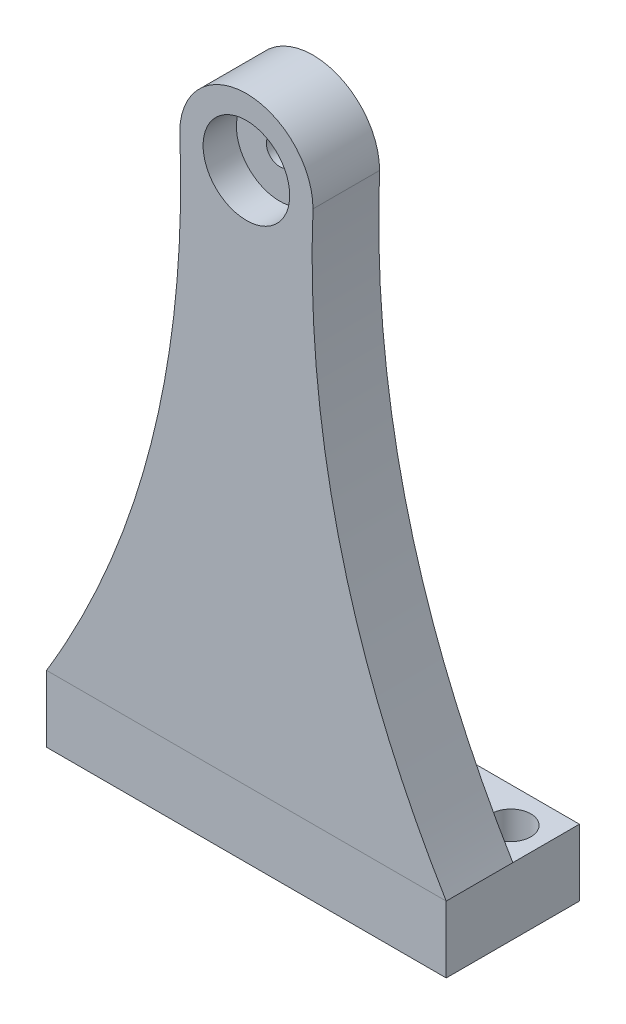
SolidWorks part; units mm, degrees
note: The reader was unsure of these and kept them because the rebuilt part matched: thickness of "Taban-Flanş1", "Taban-Flanş2", "Sac-Levha1", "Sac-Levha2", "Sheet-Metal27", "Sheet-Metal28", "Sheet-Metal29".
other "Markup1"
sketch "Sketch1" plane through (40, 90, 0) normal (0.9714, 0.2368, 0.0146) x (0.0441, -0.1197, -0.9918)
ref_plane "Ön Düzlem" through (0, 0, 0) normal (0, 0, 1) x (1, 0, 0)
ref_plane "Üst Düzlem" through (0, 0, 0) normal (0, 1, 0) x (1, 0, 0)
ref_plane "Sağ Düzlem" through (0, 0, 0) normal (1, 0, 0) x (0, 0, -1)
sketch "Çizim1" plane through (0, 0, 0) normal (0, 0, 1) x (1, 0, 0)
  line L0 (-100, 0) -> (200, 0)
  arc A0 (0, 400) -> (100, 400) centre (50, 400) cw
  circle A1 centre (50, 400) radius 10
  spline S0 degree 2 poles (-100, 0) (8.8172, 180.8736) (0, 400) knots 0 0 0 1 1 1
  spline S1 degree 2 poles (200, 0) (91.1828, 180.8736) (100, 400) knots 0 0 0 1 1 1
  point P42 (50, 400)
  dimension "D9" = 20
  dimension "D1" = 100
  dimension "D2" = 100
  dimension "D3" = 50
  dimension "D4" = 200
  dimension "D5" = 200
  dimension "D6" = 100
  dimension "D7" = 100
  dimension "D8" = 400
base flange "Taban-Flanş1" sketch "Çizim1" thickness 50 reverse thickness direction no parameters "D1"=0.7366
sketch "Çizim6" plane through (0, 0, 0) normal (0, 1, 0) x (1, 0, 0)
  line L0 (-100, 0) -> (-100, 100)
  line L1 (-100, 100) -> (200, 100)
  line L2 (200, 100) -> (200, 0)
  line L3 (-100, 0) -> (200, 0)
  circle A0 centre (-75, 73.5) radius 15
  circle A1 centre (175, 73.5) radius 15
  dimension "D3" = 30
  dimension "D4" = 30
  dimension "D1" = 300
  dimension "D2" = 100
  dimension "D5" = 25
  dimension "D6" = 25
  dimension "D7" = 73.5
  dimension "D8" = 73.5
base flange "Taban-Flanş2" sketch "Çizim6" thickness 50 reverse thickness direction no parameters "D1"=0.7366
scale "Scale1" bodies to scale 102 101 scale about origin uniform scaling yes scale factor 0.2
sketch "Sketch3" plane through (0, 0, 0) normal (0, 0, 1) x (1, 0, 0)
  circle A0 centre (10, 80) radius 6.5
  dimension "D1" = 13
extrude "Cut-Extrude1" cut sketch "Sketch3" against normal blind 5
sketch "Büküm-Çizgileri1" [suppressed] plane through (0, 0, 0) normal (0, 1, 0) x (1, 0, 0)
sketch "Sınırlandırma-Kutusu1" [suppressed] plane through (0, 0, 0) normal (0, 1, 0) x (1, 0, 0)
sheet metal parameters "Sac-Levha1" thickness 50 parameters "D1"=0.7366
flat pattern "Düz-Çoğaltma1" [suppressed]
sketch "Büküm-Çizgileri2" plane through (0, 0, 0) normal (0, 1, 0) x (1, 0, 0)
sketch3d "Sınırlandırma-Kutusu2" [suppressed]
  line L0 (220.5914, 259.5632, 0) -> (220.5914, -190.4368, 0) construction
  line L1 (-79.4086, 259.5632, 0) -> (-79.4086, -190.4368, 0) construction
  line L2 (220.5914, 259.5632, 0) -> (-79.4086, 259.5632, 0) construction
  line L3 (220.5914, -190.4368, 0) -> (-79.4086, -190.4368, 0) construction
sheet metal parameters "Sac-Levha2" thickness 50 parameters "D1"=0.7366
flat pattern "Düz-Çoğaltma2"
sketch "Büküm-Çizgileri3"
sketch3d "Sınırlandırma-Kutusu3" [suppressed]
  line L0 (-100, 50, 0) -> (200, 50, 0) construction
  line L1 (-100, 0, 0) -> (200, 0, 0) construction
  line L2 (-100, 50, 0) -> (-100, 0, 0) construction
  line L3 (200, 50, 0) -> (200, 0, 0) construction
sheet metal parameters "Sheet-Metal27" thickness 50 parameters "D1"=0.7366
flat pattern "Düz-Çoğaltma2"
sketch "Büküm-Çizgileri3"
sketch3d "Sınırlandırma-Kutusu3" [suppressed]
  line L0 (-100, 50, 0) -> (200, 50, 0) construction
  line L1 (-100, 0, 0) -> (200, 0, 0) construction
  line L2 (-100, 50, 0) -> (-100, 0, 0) construction
  line L3 (200, 50, 0) -> (200, 0, 0) construction
sheet metal parameters "Sheet-Metal28" thickness 50 parameters "D1"=0.7366, "D7"=0.7366
flat pattern "Düz-Çoğaltma1"
sketch "Büküm-Çizgileri2" plane through (0, 0, 0) normal (0, 1, 0) x (1, 0, 0)
sketch3d "Sınırlandırma-Kutusu2" [suppressed]
  line L0 (220.5914, 259.5632, 0) -> (220.5914, -190.4368, 0) construction
  line L1 (-79.4086, 259.5632, 0) -> (-79.4086, -190.4368, 0) construction
  line L2 (220.5914, 259.5632, 0) -> (-79.4086, 259.5632, 0) construction
  line L3 (220.5914, -190.4368, 0) -> (-79.4086, -190.4368, 0) construction
sheet metal parameters "Sheet-Metal29" thickness 50 parameters "D1"=0.7366, "D7"=0.7366
flat pattern "Düz-Çoğaltma1"
sketch "Büküm-Çizgileri2" plane through (0, 0, 0) normal (0, 1, 0) x (1, 0, 0)
sketch3d "Sınırlandırma-Kutusu2" [suppressed]
  line L0 (220.5914, 259.5632, 0) -> (220.5914, -190.4368, 0) construction
  line L1 (-79.4086, 259.5632, 0) -> (-79.4086, -190.4368, 0) construction
  line L2 (220.5914, 259.5632, 0) -> (-79.4086, 259.5632, 0) construction
  line L3 (220.5914, -190.4368, 0) -> (-79.4086, -190.4368, 0) construction
